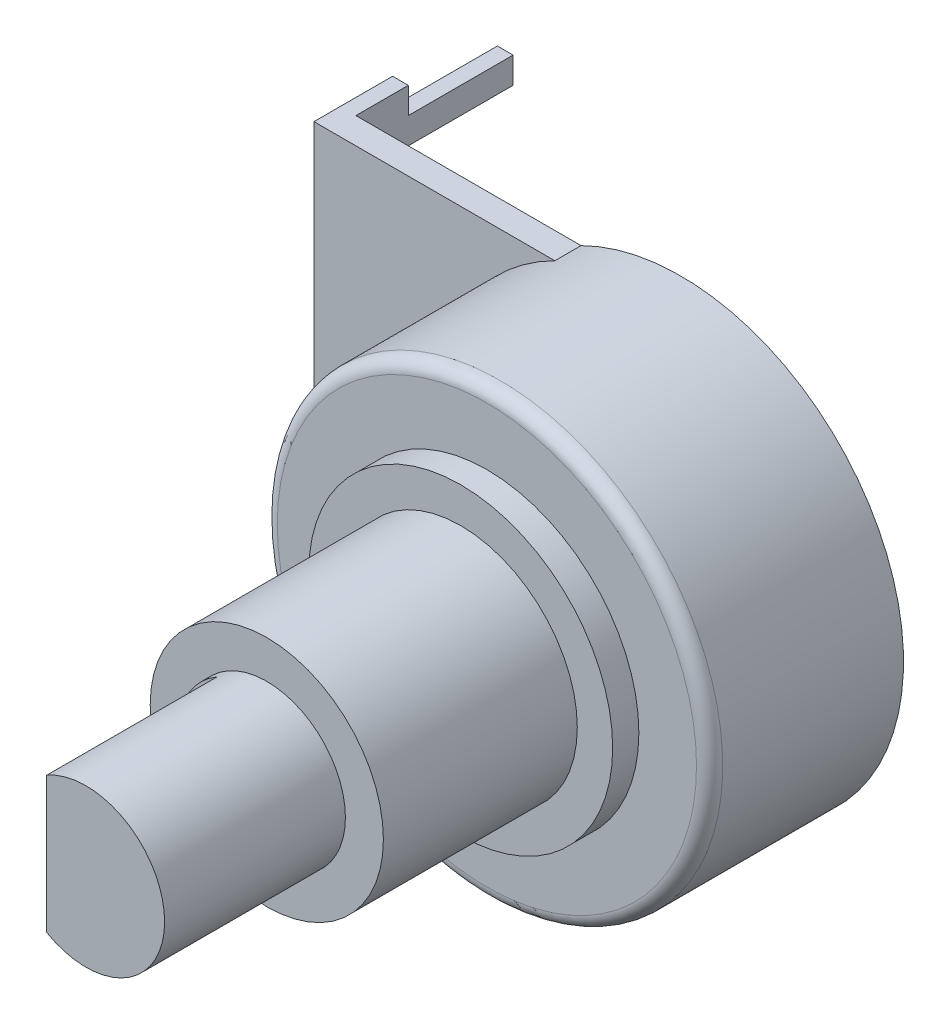
SolidWorks part; units mm, degrees
ref_plane "Спереди" through (0, 0, 0) normal (0, 0, 1) x (1, 0, 0)
ref_plane "Сверху" through (0, 0, 0) normal (0, 1, 0) x (1, 0, 0)
ref_plane "Справа" through (0, 0, 0) normal (1, 0, 0) x (0, 0, -1)
sketch "Эскиз1" plane through (0, 0, 0) normal (0, 0, 1) x (1, 0, 0)
  circle A0 centre (0, 0) radius 4.45
  dimension "D1" = 8.9
extrude "Бобышка-Вытянуть1" add sketch "Эскиз1" along normal blind 7.4
sketch "Эскиз2" plane through (0, 0, 7.4) normal (0, 0, 1) x (1, 0, 0)
  circle A0 centre (0, 0) radius 3
  dimension "D1" = 6
extrude "Бобышка-Вытянуть2" add sketch "Эскиз2" along normal blind 6.9
sketch "Эскиз3" plane through (0, 0, 14.3) normal (0, 0, 1) x (1, 0, 0)
  line L1 (-5.4207, 3.162) -> (-1.5, 3.162)
  line L2 (-5.4207, 3.162) -> (-5.4207, -3.6597)
  line L3 (-5.4207, -3.6597) -> (-1.5, -3.6597)
  line L4 (-1.5, 3.162) -> (-1.5, -3.6597)
  dimension "D1" = 1.5
extrude "Вырез-Вытянуть1" cut sketch "Эскиз3" against normal blind 6.5
sketch "Эскиз4" plane through (0, 0, 0) normal (0, 0, -1) x (-1, 0, 0)
  circle A0 centre (0, 0) radius 5.8
  dimension "D1" = 11.6
extrude "Бобышка-Вытянуть3" add sketch "Эскиз4" along normal blind 1
sketch "Эскиз5" plane through (0, 0, -1) normal (0, 0, -1) x (-1, 0, 0)
  circle A0 centre (0, 0) radius 8.5
  dimension "D1" = 17
extrude "Бобышка-Вытянуть4" add sketch "Эскиз5" along normal blind 7.4
fillet "Скругление1" radius 0.5 1 edges at (-8.5, 0, -1)
sketch "Эскиз6" plane through (0, 0, -8.4) normal (0, 0, -1) x (-1, 0, 0)
  line L1 (0, 7.6) -> (13, 7.6)
  line L2 (0, 7.6) -> (0, -7.6)
  line L3 (0, -7.6) -> (13, -7.6)
  line L4 (13, 7.6) -> (13, -7.6)
  point P4 (0, 0)
  dimension "D1" = 0
  dimension "D2" = 15.2
  dimension "D3" = 0
  dimension "D4" = 13
extrude "Бобышка-Вытянуть5" add sketch "Эскиз6" against normal blind 1
sketch "Эскиз7" plane through (0, 0, -8.4) normal (0, 0, -1) x (-1, 0, 0)
  line L0 (13, -7.6) -> (13, 7.6) construction
  line L1 (13, 7.6) -> (12.4, 7.6)
  line L2 (13, 7.6) -> (13, 4.6)
  line L3 (13, 4.6) -> (12.4, 4.6)
  line L4 (12.4, 7.6) -> (12.4, 4.6)
  line L5 (13, -1.5) -> (12.4, -1.5)
  line L6 (13, -1.5) -> (13, 1.5)
  line L7 (13, 1.5) -> (12.4, 1.5)
  line L8 (12.4, -1.5) -> (12.4, 1.5)
  line L10 (13, -7.6) -> (12.4, -7.6)
  line L11 (13, -7.6) -> (13, -4.6)
  line L12 (13, -4.6) -> (12.4, -4.6)
  line L13 (12.4, -7.6) -> (12.4, -4.6)
  point P16 (13, 0)
  point P17 (13, 0)
  dimension "D1" = 0
  dimension "D2" = 0.6
  dimension "D3" = 3
extrude "Бобышка-Вытянуть6" add sketch "Эскиз7" along normal blind 6
sketch "Эскиз8" plane through (-13, 0, 0) normal (-1, 0, 0) x (0, 0, 1)
  line L1 (-14.4, 7.6) -> (-10.4, 7.6)
  line L2 (-14.4, 7.6) -> (-14.4, 6.6)
  line L3 (-14.4, 6.6) -> (-10.4, 6.6)
  line L4 (-10.4, 7.6) -> (-10.4, 6.6)
  line L5 (-14.4, 4.6) -> (-10.4, 4.6)
  line L6 (-14.4, 4.6) -> (-14.4, 5.6)
  line L7 (-14.4, 5.6) -> (-10.4, 5.6)
  line L8 (-10.4, 4.6) -> (-10.4, 5.6)
  line L9 (-14.4, 1.5) -> (-10.4, 1.5)
  line L10 (-14.4, 1.5) -> (-14.4, 0.5)
  line L11 (-14.4, 0.5) -> (-10.4, 0.5)
  line L12 (-10.4, 1.5) -> (-10.4, 0.5)
  line L13 (-14.4, -1.5) -> (-10.4, -1.5)
  line L14 (-14.4, -1.5) -> (-14.4, -0.5)
  line L15 (-14.4, -0.5) -> (-10.4, -0.5)
  line L16 (-10.4, -1.5) -> (-10.4, -0.5)
  line L17 (-14.4, -4.6) -> (-10.4, -4.6)
  line L18 (-14.4, -4.6) -> (-14.4, -5.6)
  line L19 (-14.4, -5.6) -> (-10.4, -5.6)
  line L20 (-10.4, -4.6) -> (-10.4, -5.6)
  line L21 (-14.4, -7.6) -> (-10.4, -7.6)
  line L22 (-14.4, -7.6) -> (-14.4, -6.6)
  line L23 (-14.4, -6.6) -> (-10.4, -6.6)
  line L24 (-10.4, -7.6) -> (-10.4, -6.6)
  dimension "D1" = 4
  dimension "D2" = 1
extrude "Вырез-Вытянуть2" cut sketch "Эскиз8" against normal through all
